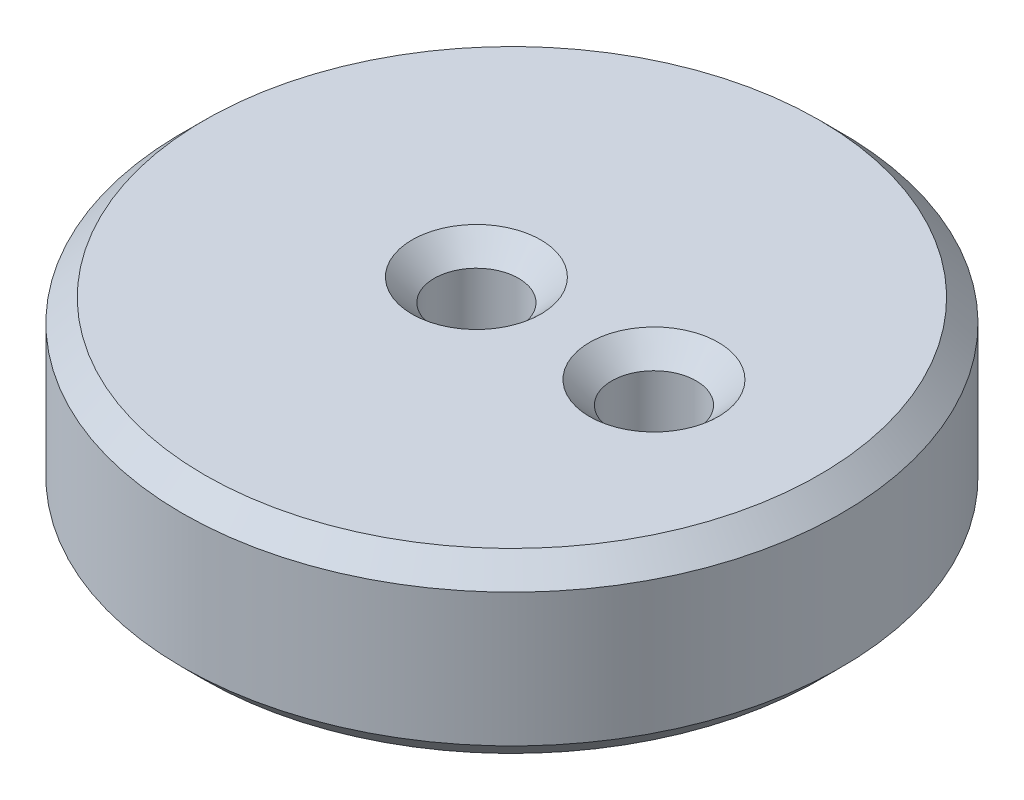
SolidWorks part; units mm, degrees
ref_plane "前视基准面" through (0, 0, 0) normal (0, 0, 1) x (1, 0, 0)
ref_plane "上视基准面" through (0, 0, 0) normal (0, 1, 0) x (1, 0, 0)
ref_plane "右视基准面" through (0, 0, 0) normal (1, 0, 0) x (0, 0, -1)
other "Configuration Table"
sketch "草图1" plane through (0, 0, 0) normal (0, 1, 0) x (1, 0, 0)
  line L0 (1.2, 6.4178) -> (1.2, -6.4114) construction
  line L1 (-5.7349, 0) -> (5.8104, 0) construction
  circle A0 centre (0, 0) radius 7.425
  circle A1 centre (3.2, 0) radius 0.95
  circle A2 centre (-0.8, 0) radius 0.95
  dimension "D1" = 14.85
  dimension "D3" = 4
  dimension "D4" = 1.9
  dimension "D2" = 1.2
extrude "凸台-拉伸1" add sketch "草图1" along normal blind 4
chamfer "倒角1" distance 0.5 angle 45 6 edges at (0, 0, 7.425) (0, 4, 7.425) (-0.8, 0, -0.95) (3.2, 0, 0.95) (-0.8, 4, -0.95) (3.2, 4, 0.95)
ref_axis "基准轴1" through (0, 3.5, 0) along (0, -1, 0)
sketch "草图2" plane through (0, 0, 0) normal (0, 1, 0) x (1, 0, 0)
  line L0 (-5.9042, 0) -> (6.2358, 0) construction
